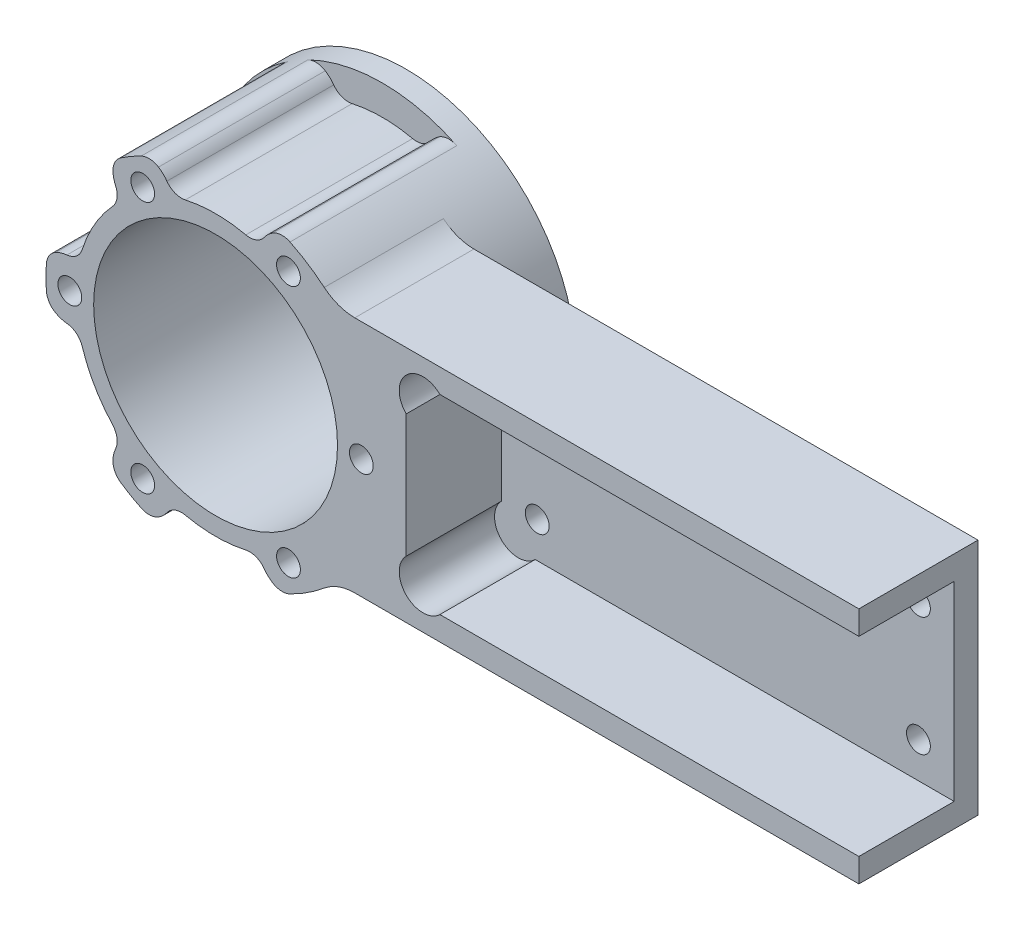
SolidWorks part; units mm, degrees
material "1060 Alloy"
ref_plane "Front Plane" through (0, 0, 0) normal (0, 0, 1) x (1, 0, 0)
ref_plane "Top Plane" through (0, 0, 0) normal (0, 1, 0) x (1, 0, 0)
ref_plane "Right Plane" through (0, 0, 0) normal (1, 0, 0) x (0, 0, -1)
sketch "Sketch1" plane through (0, 0, 0) normal (0, 0, 1) x (1, 0, 0)
  line L0 (32.1711, 31.75) -> (171.45, 31.75)
  line L1 (32.1711, -31.75) -> (171.45, -31.75)
  line L3 (171.45, 31.75) -> (171.45, 25.4)
  line L4 (171.45, -31.75) -> (171.45, -25.4)
  line L5 (171.45, 31.75) -> (171.45, -31.75) construction
  line L6 (171.45, 25.4) -> (50.8, 25.4)
  line L7 (50.8, 25.4) -> (50.8, -25.4)
  line L8 (50.8, -25.4) -> (171.45, -25.4)
  line L9 (171.45, 25.4) -> (171.45, -25.4)
  circle A0 centre (0, 0) radius 32.5
  arc A1 (32.1711, 31.75) -> (32.1711, -31.75) centre (0, 0) ccw
  point P3 (171.45, 0)
  dimension "D1" = 65
  dimension "D4" = 12.7
  dimension "D6" = 50.8
  dimension "D2" = 63.5
  dimension "D3" = 120.65
  dimension "D5" = 6.35
extrude "Boss-Extrude2" add sketch "Sketch1" along normal blind 6.35 contours L0 A1 L1 L4 L8 L7 L6 L3 A0 | L9 L6 L7 L8 region at (37.7479, 0, 0) region at (111.125, 0, 0)
extrude "Boss-Extrude3" add sketch "Sketch1<3>" along normal blind 25.4 from surface contours L0 A1 L1 L4 L8 L7 L6 L3 A0 region at (37.7479, 0, 0) starting at face at (82.4678, 0, 6.35)
sketch "Sketch1<3>" plane through (0, 0, 0) normal (0, 0, 1) x (1, 0, 0) same geometry as "Sketch1"
sketch "Sketch2" plane through (0, 0, 6.35) normal (0, 0, 1) x (1, 0, 0)
  line L0 (171.45, -25.4) -> (171.45, 25.4) construction
  line L1 (50.8, -25.4) -> (50.8, 25.4) construction
  line L4 (50.8, 25.4) -> (171.45, 25.4) construction
  line L5 (50.8, 25.4) -> (171.45, 25.4) construction
  line L6 (171.45, -25.4) -> (50.8, -25.4) construction
  line L7 (171.45, -25.4) -> (50.8, -25.4) construction
  circle A0 centre (60.325, 15.875) radius 3.175
  circle A1 centre (161.925, 15.875) radius 3.175
  circle A2 centre (161.925, -15.875) radius 3.175
  circle A3 centre (60.325, -15.875) radius 3.175
  circle A15 centre (0, 0) radius 38.85 construction
  arc A16 (32.1711, 31.75) -> (32.1711, -31.75) centre (0, 0) ccw construction
  dimension "D1" = 6.35
  dimension "D2" = 6.35
  dimension "D4" = 9.525
  dimension "D5" = 9.525
  dimension "D6" = 9.525
  dimension "D3" = 9.525
  dimension "D7" = 9.525
  dimension "D8" = 9.525
extrude "Cut-Extrude1" cut sketch "Sketch2" against normal through all and the other way through all
sketch "Sketch3" plane through (0, 0, 31.75) normal (0, 0, 1) x (1, 0, 0)
  line L0 (50.8, 25.4) -> (59.7803, 16.4197) construction
  line L1 (50.8, 25.4) -> (171.45, 25.4) construction
  line L2 (50.8, 0) -> (32.5, 0) construction
  line L3 (50.8, -25.4) -> (50.8, 25.4) construction
  circle A0 centre (55.2901, 20.9099) radius 6.35
  circle A1 centre (0, 0) radius 32.5 construction
  circle A2 centre (55.2901, -20.9099) radius 6.35
  dimension "D1" = 12.7
  dimension "D2" = 45
extrude "Cut-Extrude2" cut sketch "Sketch3" against normal up to surface (25.4 mm away) up to face at (63.5, -15.875, 6.35)
sketch "Sketch4" plane through (0, 0, 0) normal (0, 0, -1) x (-1, 0, 0)
  line L0 (-31.75, 54.9926) -> (0, 0) construction
  line L1 (0, 0) -> (31.75, 54.9926) construction
  line L2 (-32.1711, -31.75) -> (-171.45, -31.75) construction
  line L3 (0, 0) -> (63.5, 0) construction
  line L4 (0, 0) -> (31.75, -54.9926) construction
  line L9 (-51.2937, 31.75) -> (-32.1711, 31.75)
  line L10 (-32.1711, 31.75) -> (-171.45, 31.75) construction
  line L11 (-32.1711, -31.75) -> (-51.2937, -31.75)
  line L12 (0, 0) -> (-63.5, 0) construction
  line L13 (0, 0) -> (-31.75, -54.9926) construction
  arc A1 (-40.8506, -48.6156) -> (-40.8506, 48.6156) centre (0, 0) ccw construction
  arc A2 (-20.7603, 56.6402) -> (-38.6717, 46.2991) centre (-31.75, 54.9926) ccw
  arc A8 (38.6717, 46.2991) -> (20.7603, 56.6402) centre (31.75, 54.9926) ccw
  arc A9 (59.432, -10.3411) -> (59.432, 10.3411) centre (63.5, 0) ccw
  arc A10 (20.7603, -56.6402) -> (38.6717, -46.2991) centre (31.75, -54.9926) ccw
  arc A11 (-38.6717, -46.2991) -> (-20.7603, -56.6402) centre (-31.75, -54.9926) ccw
  circle A13 centre (-31.75, 54.9926) radius 4.7625
  arc A14 (-38.6717, 46.2991) -> (-51.2937, 31.75) centre (0, 0) ccw
  circle A15 centre (31.75, 54.9926) radius 4.7625
  arc A16 (-32.1711, -31.75) -> (-32.1711, 31.75) centre (0, 0) ccw construction
  arc A17 (20.7603, 56.6402) -> (-20.7603, 56.6402) centre (0, 0) ccw
  circle A18 centre (63.5, 0) radius 4.7625
  circle A19 centre (31.75, -54.9926) radius 4.7625
  arc A20 (59.432, 10.3411) -> (38.6717, 46.2991) centre (0, 0) ccw
  arc A21 (38.6717, -46.2991) -> (59.432, -10.3411) centre (0, 0) ccw
  circle A22 centre (-31.75, -54.9926) radius 4.7625
  arc A23 (-20.7603, -56.6402) -> (20.7603, -56.6402) centre (0, 0) ccw
  arc A24 (-32.1711, -31.75) -> (-32.1711, 31.75) centre (0, 0) ccw
  arc A25 (-51.2937, -31.75) -> (-38.6717, -46.2991) centre (0, 0) ccw
  circle A26 centre (-63.5, 0) radius 4.7625
  point P48 (0, 0)
  dimension "D1" = 6.35
  dimension "D2" = 127
  dimension "D3" = 6
  dimension "D8" = 60.325
  dimension "D9" = 9.525
extrude "Boss-Extrude5" [suppressed] add sketch "Sketch4" against normal blind 6.35
fillet "Fillet1" radius 12.7 2 edges at (32.1711, -31.75, 15.875) (32.1711, 31.75, 15.875)
fillet "Fillet2" [suppressed] radius 12.7
sketch "Sketch5" plane through (0, 0, 0) normal (0, 0, -1) x (-1, 0, 0)
  arc A0 (-28.9644, -34.7002) -> (-28.9644, 34.7002) centre (0, 0) ccw construction
  arc A1 (-28.9644, -34.7002) -> (-28.9644, 34.7002) centre (0, 0) ccw
  circle A6 centre (0, 0) radius 32.5 construction
  circle A11 centre (0, 0) radius 32.5
  arc A12 (-28.9644, 34.7002) -> (-28.9644, -34.7002) centre (0, 0) ccw
  arc A13 (-28.9644, -34.7002) -> (-37.1027, -31.75) centre (-37.1027, -44.45) ccw construction
extrude "Boss-Extrude6" add sketch "Sketch5" along normal blind 19.05
sketch "Sketch6" plane through (0, 0, -19.05) normal (0, 0, -1) x (-1, 0, 0)
  circle A0 centre (0, 0) radius 32.5 construction
  circle A1 centre (0, 0) radius 32.5
  circle A2 centre (0, 0) radius 27.5
  dimension "D1" = 55
extrude "Boss-Extrude7" add sketch "Sketch6" against normal blind 2.54
sketch "Sketch7" plane through (0, 0, -19.05) normal (0, 0, -1) x (-1, 0, 0)
  circle A0 centre (0, 0) radius 67.6783
  dimension "D1" = 135.3566
sketch "Sketch9" plane through (0, 0, -19.05) normal (0, 0, -1) x (-1, 0, 0)
  line L0 (0, 0) -> (38.85, 0) construction
  line L1 (0, 45.2) -> (0, 32.5) construction
  circle A2 centre (0, 0) radius 38.85 construction
  circle A3 centre (38.85, 0) radius 3.175
  circle A4 centre (-60.325, 15.875) radius 3.175 construction
  circle A5 centre (19.425, -33.6451) radius 3.175
  circle A6 centre (-19.425, -33.6451) radius 3.175
  circle A7 centre (-38.85, 0) radius 3.175
  circle A8 centre (-19.425, 33.6451) radius 3.175
  circle A9 centre (19.425, 33.6451) radius 3.175
  circle A10 centre (0, 0) radius 32.5 construction
  circle A11 centre (0, 0) radius 32.5 construction
  circle A12 centre (0, 0) radius 45.2 construction
  point P16 (0, 38.85)
  point P27 (0, 0)
  dimension "D1" = 6
extrude "Cut-Extrude3" cut sketch "Sketch9" against normal through all both and the other way through all
sketch "Sketch10" plane through (0, 0, 31.75) normal (0, 0, 1) x (1, 0, 0)
  circle A2 centre (0, 0) radius 37.2625
  arc A3 (11.6804, 35.3845) -> (-11.6804, 35.3845) centre (0, 0) ccw
  circle A5 centre (19.425, 33.6451) radius 7.9375
  arc A6 (18.0125, 41.4559) -> (11.6804, 35.3845) centre (19.425, 33.6451) ccw
  circle A8 centre (-19.425, 33.6451) radius 7.9375
  arc A9 (-26.8956, 36.3272) -> (-24.8036, 27.8078) centre (-19.425, 33.6451) ccw
  circle A11 centre (-38.85, 0) radius 7.9375
  arc A12 (-44.9081, -5.1287) -> (-36.4841, -7.5767) centre (-38.85, 0) ccw
  circle A14 centre (-19.425, -33.6451) radius 7.9375
  arc A15 (-18.0125, -41.4559) -> (-11.6804, -35.3845) centre (-19.425, -33.6451) ccw
  arc A16 (28.9644, 34.7002) -> (28.9644, -34.7002) centre (0, 0) ccw construction
  circle A17 centre (19.425, -33.6451) radius 7.9375
  arc A18 (11.6804, -35.3845) -> (18.0125, -41.4559) centre (19.425, -33.6451) ccw
  arc A19 (18.0125, 41.4559) -> (-18.0125, 41.4559) centre (0, 0) ccw
  arc A20 (-24.8036, -27.8078) -> (-26.8956, -36.3272) centre (-19.425, -33.6451) ccw
  arc A21 (-11.6804, -35.3845) -> (11.6804, -35.3845) centre (0, 0) ccw
  arc A22 (-36.4841, 7.5767) -> (-44.9081, 5.1287) centre (-38.85, 0) ccw
  arc A23 (-11.6804, 35.3845) -> (-18.0125, 41.4559) centre (-19.425, 33.6451) ccw
  arc A24 (-24.8036, 27.8078) -> (-36.4841, 7.5767) centre (0, 0) ccw
  arc A25 (-36.4841, -7.5767) -> (-24.8036, -27.8078) centre (0, 0) ccw
  arc A26 (-26.8956, 36.3272) -> (-44.9081, 5.1287) centre (0, 0) ccw
  arc A27 (-44.9081, -5.1287) -> (-26.8956, -36.3272) centre (0, 0) ccw
  arc A28 (-18.0125, -41.4559) -> (18.0125, -41.4559) centre (0, 0) ccw
  dimension "D1" = 4.7625
  dimension "D2" = 4.7625
  dimension "D3" = 4.7625
  dimension "D4" = 4.7625
  dimension "D5" = 4.7625
  dimension "D6" = 4.7625
extrude "Cut-Extrude4" cut sketch "Sketch10" against normal offset from surface (44.45 mm away) 6.35 contours A3 A23 A19 A6 | A9 A24 A22 A26 | A12 A25 A20 A27 | A15 A21 A18 A28 up to face at (-42.025, 0, -19.05)
fillet "Fillet3" radius 4.7625 16 edges at (18.0125, 41.4559, 9.525) (11.6804, 35.3845, 9.525) (-11.6804, 35.3845, 9.525) (-18.0125, 41.4559, 9.525) (-26.8956, 36.3272, 9.525) (-24.8036, 27.8078, 9.525) (-44.9081, 5.1287, 9.525) (-36.4841, 7.5767, 9.525) (-44.9081, -5.1287, 9.525) (-36.4841, -7.5767, 9.525) (-24.8036, -27.8078, 9.525) (-26.8956, -36.3272, 9.525) (-18.0125, -41.4559, 9.525) (-11.6804, -35.3845, 9.525) (11.6804, -35.3845, 9.525) (18.0125, -41.4559, 9.525)
